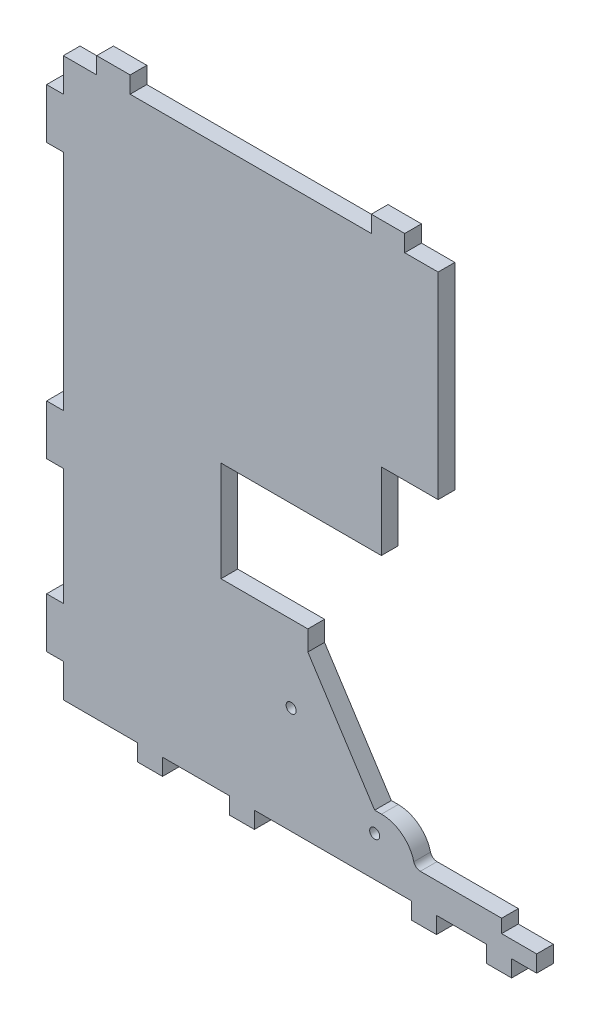
SolidWorks part; units mm, degrees
ref_plane "Plan de face" through (0, 0, 0) normal (0, 0, 1) x (1, 0, 0)
ref_plane "Plan de dessus" through (0, 0, 0) normal (0, 1, 0) x (1, 0, 0)
ref_plane "Plan de droite" through (0, 0, 0) normal (1, 0, 0) x (0, 0, -1)
sketch "Esquisse1" plane through (0, 0, 0) normal (0, 0, 1) x (1, 0, 0)
  line L0 (11, 49) -> (31, 18)
  line L1 (0, 0) -> (37, 0)
  line L2 (0, 0) -> (0, 55)
  line L3 (0, 55) -> (11, 55)
  line L4 (37, 0) -> (37, 18)
  line L6 (11, 55) -> (11, 49)
  line L7 (31, 18) -> (37, 18)
  circle A0 centre (6, 32) radius 1.5
  circle A1 centre (31, 12) radius 1.5
  dimension "D3" = 20
  dimension "D4" = 3
  dimension "D1" = 6
  dimension "D2" = 55
  dimension "D5" = 12
  dimension "D6" = 6
  dimension "D7" = 25
  dimension "D8" = 11
  dimension "D9" = 6
  dimension "D10" = 6
  dimension "D11" = 6
extrude "Boss.-Extru.1" add sketch "Esquisse1" along normal blind 5
sketch "Esquisse2" plane through (0, 0, 5) normal (0, 0, 1) x (1, 0, 0)
  line L0 (37, 18) -> (31, 18) construction
  line L1 (37, 0) -> (42, 0)
  line L2 (37, 0) -> (37, 18)
  line L3 (49.5, 0) -> (64.5, 0)
  line L4 (11, 55) -> (0, 55) construction
  line L5 (72, 0) -> (72, -5)
  line L6 (72, -5) -> (64.5, -5)
  line L7 (64.5, 0) -> (64.5, -5)
  line L8 (72, 0) -> (79.5, 0)
  line L9 (49.5, 0) -> (49.5, -5)
  line L10 (49.5, -5) -> (42, -5)
  line L11 (42, 0) -> (42, -5)
  line L12 (0, 0) -> (-5, 0)
  line L13 (0, 0) -> (0, 55)
  line L14 (0, 55) -> (-15, 55)
  line L15 (40, 167) -> (50, 167)
  line L16 (-12.5, 0) -> (-32.5, 0)
  line L17 (-40, 0) -> (-40, -5)
  line L18 (-15, 55) -> (-15, 85)
  line L19 (-40, -5) -> (-32.5, -5)
  line L20 (-62.19, 0) -> (-62.19, 10)
  line L21 (-62.19, 167) -> (-52.19, 167)
  line L22 (-32.5, 0) -> (-32.5, -5)
  line L23 (33, 85) -> (-15, 85)
  line L24 (50, 167) -> (50, 108)
  line L25 (-12.5, 0) -> (-12.5, -5)
  line L26 (-12.5, -5) -> (-5, -5)
  line L27 (-5, 0) -> (-5, -5)
  line L28 (-40, 0) -> (-62.19, 0)
  line L29 (-52.19, 167) -> (-52.19, 172)
  line L30 (-52.19, 172) -> (-42.19, 172)
  line L31 (-42.19, 167) -> (-42.19, 172)
  line L32 (-42.19, 167) -> (30, 167)
  line L33 (40, 167) -> (40, 172)
  line L34 (40, 172) -> (30, 172)
  line L35 (30, 167) -> (30, 172)
  line L36 (-62.19, 157) -> (-62.19, 167)
  line L37 (-62.19, 10) -> (-67.19, 10)
  line L38 (33, 85) -> (33, 108)
  line L39 (33, 108) -> (50, 108)
  line L40 (37, 18) -> (43, 18)
  line L41 (-62.19, 25) -> (-67.19, 25)
  line L42 (-67.19, 10) -> (-67.19, 25)
  line L43 (-62.19, 60) -> (-67.19, 60)
  line L44 (-62.19, 25) -> (-62.19, 60)
  line L45 (-62.19, 75) -> (-67.19, 75)
  line L46 (-67.19, 60) -> (-67.19, 75)
  line L47 (-62.19, 157) -> (-67.19, 157)
  line L48 (-62.19, 75) -> (-62.19, 142)
  line L49 (-62.19, 142) -> (-67.19, 142)
  line L50 (-67.19, 157) -> (-67.19, 142)
  line L51 (79.5, 0) -> (79.5, 5)
  line L52 (43, 18) -> (43, 9)
  line L53 (43, 9) -> (69, 9)
  line L56 (69, 9) -> (69, 5)
  line L57 (69, 5) -> (79.5, 5)
  circle A0 centre (31, 12) radius 1.5 construction
  dimension "D24" = 3
  dimension "D25" = 12
  dimension "D1" = 42.5
  dimension "D2" = 7.5
  dimension "D3" = 5
  dimension "D4" = 5
  dimension "D5" = 15
  dimension "D6" = 15
  dimension "D7" = 30
  dimension "D8" = 167
  dimension "D9" = 23
  dimension "D10" = 5
  dimension "D11" = 20
  dimension "D12" = 62.19
  dimension "D13" = 50
  dimension "D14" = 5
  dimension "D15" = 10
  dimension "D16" = 10
  dimension "D17" = 10
  dimension "D18" = 17
  dimension "D19" = 10
  dimension "D20" = 10
  dimension "D21" = 35
  dimension "D22" = 15
  dimension "D23" = 5
  dimension "D26" = 5
  dimension "D27" = 26
extrude "Boss.-Extru.2" add sketch "Esquisse2" against normal blind 5
fillet "Congé1" radius 10 1 edges at (43, 18, 2.5)
fillet "Congé2" radius 2 1 edges at (43, 9, 2.5)
